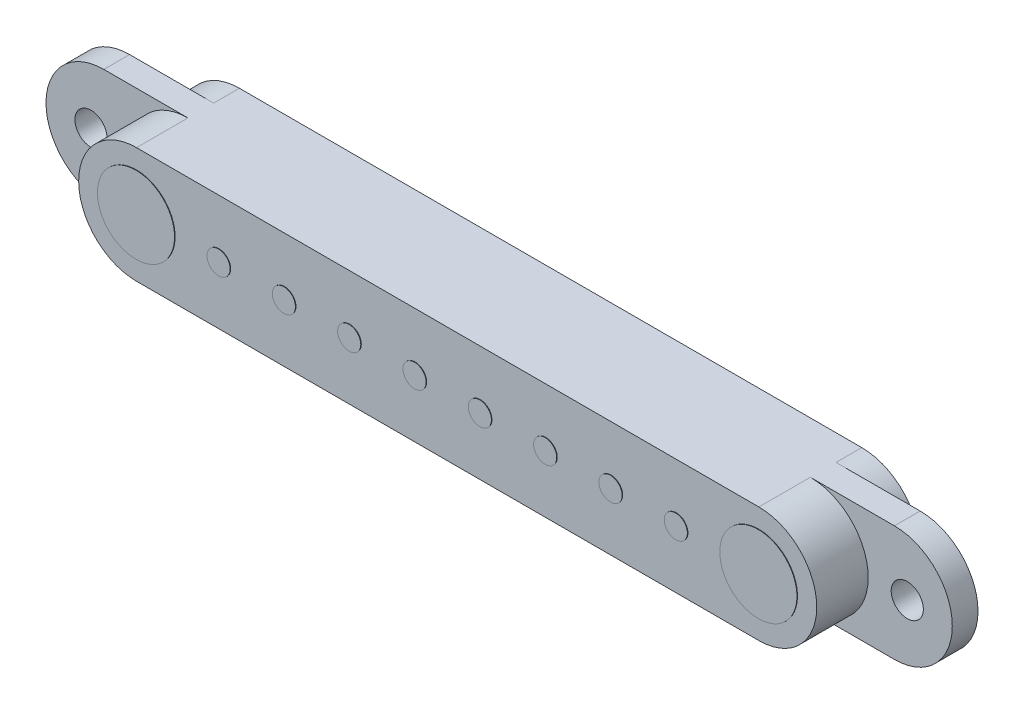
SolidWorks part; units mm, degrees
note: The reader was unsure of these and kept them because the rebuilt part matched: shared geometry of "草图2<3>".
ref_plane "前视基准面" through (0, 0, 0) normal (0, 0, 1) x (1, 0, 0)
ref_plane "上视基准面" through (0, 0, 0) normal (0, 1, 0) x (1, 0, 0)
ref_plane "右视基准面" through (0, 0, 0) normal (1, 0, 0) x (0, 0, -1)
sketch "草图2" plane through (0, 0, 0) normal (0, 0, 1) x (1, 0, 0)
  line L0 (-12.1, 0) -> (12.1, 0) construction
  line L1 (-12.1, 2.25) -> (12.1, 2.25)
  line L2 (-12.1, -2.25) -> (12.1, -2.25)
  line L3 (-15.37, 0) -> (15.37, 0) construction
  line L4 (-15.37, 2.25) -> (15.37, 2.25)
  line L5 (-15.37, -2.25) -> (15.37, -2.25)
  line L6 (0, 0) -> (0, 7.5362) construction
  arc A0 (-12.1, 2.25) -> (-12.1, -2.25) centre (-12.1, 0) ccw
  arc A1 (12.1, -2.25) -> (12.1, 2.25) centre (12.1, 0) ccw
  arc A2 (-15.37, 2.25) -> (-15.37, -2.25) centre (-15.37, 0) ccw
  arc A3 (15.37, -2.25) -> (15.37, 2.25) centre (15.37, 0) ccw
  circle A6 centre (-15.87, 0) radius 0.625
  circle A7 centre (15.87, 0) radius 0.625
  point P2 (0, 0)
  point P10 (0, 0)
  dimension "D5" = 31.74
  dimension "D6" = 1.25
  dimension "D1" = 4.5
  dimension "D2" = 24.2
  dimension "D3" = 30.74
  dimension "D4" = 4.5
  dimension "D7" = 0
extrude "凸台-拉伸1" add sketch "草图2" against normal blind 4 contours A0 L2 A1 L1
extrude "凸台-拉伸2" add sketch "草图2<3>" against normal blind 1 from offset 2 contours A2 L5 A3 L4 | A6 | A7 offset against normal yes
sketch "草图2<3>" plane through (0, 0, 0) normal (0, 0, 1) x (1, 0, 0) same geometry as "草图2"
sketch "草图4" plane through (0, 0, -4) normal (0, 0, -1) x (-1, 0, 0)
  line L0 (-18.0926, 0) -> (19.6809, 0) construction
  line L1 (0, 0) -> (0, 5.1514) construction
  line L2 (-8.89, 0) -> (-6.35, 0) construction
  circle A0 centre (-8.89, 0) radius 0.45
  circle A1 centre (-6.35, 0) radius 0.45
  circle A2 centre (-3.81, 0) radius 0.45
  circle A3 centre (-1.27, 0) radius 0.45
  circle A4 centre (1.27, 0) radius 0.45
  circle A5 centre (3.81, 0) radius 0.45
  circle A6 centre (6.35, 0) radius 0.45
  circle A7 centre (8.89, 0) radius 0.45
  dimension "D1" = 0.9
  dimension "D3" = 8
  dimension "D2" = 8.89
  dimension "D4" = 2.54
extrude "凸台-拉伸3" add sketch "草图4" along normal blind 1.5 and the other way offset from surface (4.02 mm away) 0.02 other way up to face at (0, 0, 0)
sketch "草图5" plane through (0, 0, 0) normal (0, 0, 1) x (1, 0, 0)
  line L0 (-18.8071, 0) -> (20.7184, 0) construction
  line L1 (0, 0) -> (0, 5.8863) construction
  circle A0 centre (-12.1, 0) radius 1.5
  circle A1 centre (12.1, 0) radius 1.5
  dimension "D1" = 24.2
  dimension "D2" = 3
extrude "凸台-拉伸4" add sketch "草图5" along normal blind 0.02
